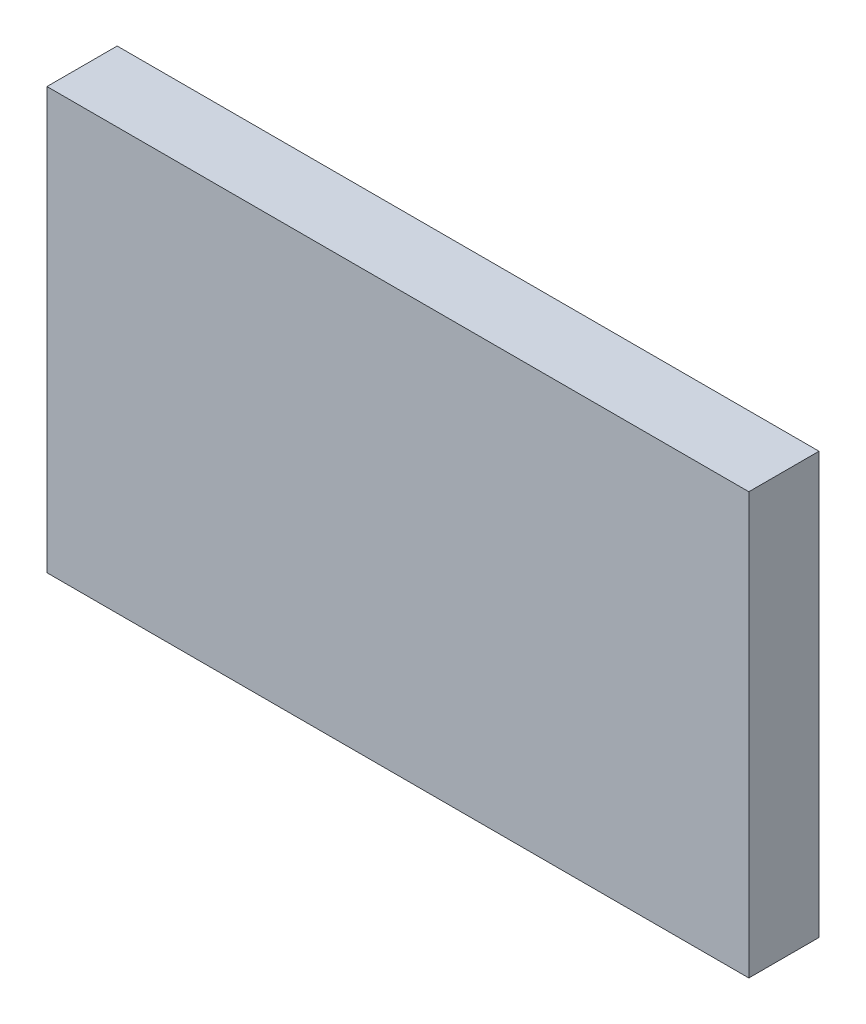
SolidWorks part; units mm, degrees
ref_plane "Plan de face" through (0, 0, 0) normal (0, 0, 1) x (1, 0, 0)
ref_plane "Plan de dessus" through (0, 0, 0) normal (0, 1, 0) x (1, 0, 0)
ref_plane "Plan de droite" through (0, 0, 0) normal (1, 0, 0) x (0, 0, -1)
sketch "Esquisse1" plane through (0, 0, 0) normal (0, 0, 1) x (1, 0, 0)
  line L1 (209.4675, 88.6738) -> (9.4675, 88.6738)
  line L2 (209.4675, 88.6738) -> (209.4675, -31.3262)
  line L3 (209.4675, -31.3262) -> (9.4675, -31.3262)
  line L4 (9.4675, 88.6738) -> (9.4675, -31.3262)
extrude "Boss.-Extru.1" add sketch "Esquisse1" along normal blind 20
sketch "Esquisse2" plane through (0, 0, 20) normal (0, 0, 1) x (1, 0, 0)
  line L0 (209.4675, -31.3262) -> (209.4675, 88.6738) construction
  line L1 (187.2577, 38.6738) -> (209.4675, 38.6738)
  line L2 (187.2577, 38.6738) -> (187.2577, 18.6738)
  line L3 (187.2577, 18.6738) -> (209.4675, 18.6738)
  line L4 (209.4675, 38.6738) -> (209.4675, 18.6738)
  line L5 (209.4675, 88.6738) -> (9.4675, 88.6738) construction
  line L7 (9.4675, -31.3262) -> (209.4675, -31.3262) construction
  dimension "D1" = 50
  dimension "D2" = 50
ref_plane "Plan1" through (209.4675, -31.3262, 0) normal (0, 1, 0) x (1, 0, 0)
